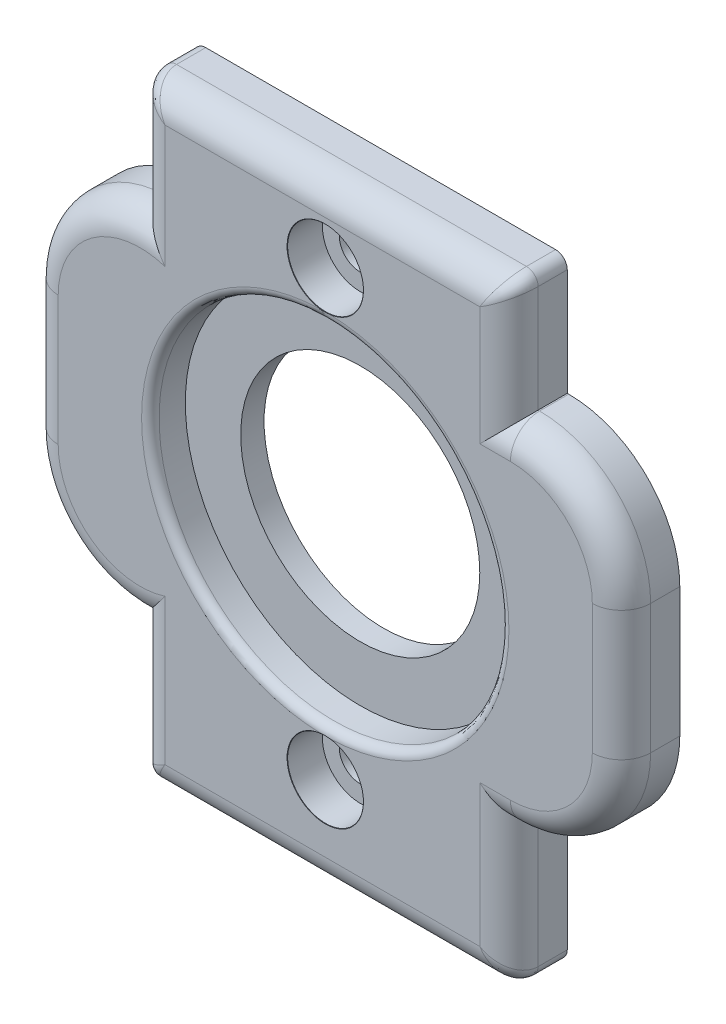
SolidWorks part; units mm, degrees
ref_plane "Front Plane" through (0, 0, 0) normal (0, 0, 1) x (1, 0, 0)
ref_plane "Top Plane" through (0, 0, 0) normal (0, 1, 0) x (1, 0, 0)
ref_plane "Right Plane" through (0, 0, 0) normal (1, 0, 0) x (0, 0, -1)
sketch "Sketch1" plane through (0, 0, 0) normal (0, 0, 1) x (1, 0, 0)
  line L0 (-13.25, 13.25) -> (14.75, 13.25) construction
  line L5 (14.75, -39.25) -> (-15.25, -39.25) construction
  line L6 (15.75, 12.25) -> (15.75, -38.25) construction
  line L7 (-15.25, 13.25) -> (14.75, 13.25)
  line L8 (14.75, -39.25) -> (-15.25, -39.25)
  line L9 (15.75, 12.25) -> (15.75, -38.25)
  line L10 (-16.25, 12.25) -> (-16.25, -38.25)
  arc A0 (15.75, 12.25) -> (14.75, 13.25) centre (14.75, 12.25) ccw construction
  arc A1 (-16.25, 12.25) -> (-15.25, 13.25) centre (-15.25, 12.25) cw
  arc A2 (-16.25, -38.25) -> (-15.25, -39.25) centre (-15.25, -38.25) ccw construction
  arc A3 (14.75, -39.25) -> (15.75, -38.25) centre (14.75, -38.25) ccw construction
  arc A4 (15.75, 12.25) -> (14.75, 13.25) centre (14.75, 12.25) ccw
  arc A6 (-16.25, -38.25) -> (-15.25, -39.25) centre (-15.25, -38.25) ccw
  arc A7 (14.75, -39.25) -> (15.75, -38.25) centre (14.75, -38.25) ccw
  dimension "D1" = 1
extrude "Boss-Extrude1" add sketch "Sketch1" along normal blind 5
sketch "Sketch6" plane through (0, 0, 0) normal (0, 0, 1) x (1, 0, 0)
  line L0 (15.875, 3.0748) -> (14.732, 3.0748) construction
  line L1 (14.732, 3.0748) -> (14.732, -27.075) construction
  line L2 (14.732, -27.075) -> (15.875, -27.075) construction
  line L3 (25.4, -17.55) -> (25.4, -6.4502) construction
  line L4 (-14.732, -27.075) -> (-14.732, 3.0748) construction
  line L5 (-14.732, 3.0748) -> (-15.875, 3.0748) construction
  line L6 (-25.4, -6.4502) -> (-25.4, -17.55) construction
  line L7 (-15.875, -27.075) -> (-14.732, -27.075) construction
  line L8 (15.875, 3.0748) -> (14.732, 3.0748)
  line L9 (14.732, 3.0748) -> (14.732, -27.075)
  line L10 (14.732, -27.075) -> (15.875, -27.075)
  line L11 (25.4, -17.55) -> (25.4, -6.4502)
  line L12 (-14.732, -27.075) -> (-14.732, 3.0748)
  line L13 (-14.732, 3.0748) -> (-15.875, 3.0748)
  line L14 (-25.4, -6.4502) -> (-25.4, -17.55)
  line L15 (-15.875, -27.075) -> (-14.732, -27.075)
  arc A0 (15.875, -27.075) -> (25.4, -17.55) centre (15.875, -17.55) ccw construction
  arc A1 (25.4, -6.4502) -> (15.875, 3.0748) centre (15.875, -6.4502) ccw construction
  arc A2 (-15.875, 3.0748) -> (-25.4, -6.4502) centre (-15.875, -6.4502) ccw construction
  arc A3 (-25.4, -17.55) -> (-15.875, -27.075) centre (-15.875, -17.55) ccw construction
  arc A4 (15.875, -27.075) -> (25.4, -17.55) centre (15.875, -17.55) ccw
  arc A5 (25.4, -6.4502) -> (15.875, 3.0748) centre (15.875, -6.4502) ccw
  arc A6 (-15.875, 3.0748) -> (-25.4, -6.4502) centre (-15.875, -6.4502) ccw
  arc A7 (-25.4, -17.55) -> (-15.875, -27.075) centre (-15.875, -17.55) ccw
sketch "Sketch7" plane through (0, 0, 5) normal (0, 0, 1) x (1, 0, 0)
  line L0 (-14.732, 3.0748) -> (14.732, 3.0748)
  line L1 (-14.732, -27.075) -> (14.732, -27.075)
  line L4 (15.875, 3.0748) -> (14.732, 3.0748)
  line L5 (14.732, 3.0748) -> (14.732, -27.075)
  line L6 (14.732, -27.075) -> (15.875, -27.075)
  line L7 (25.4, -17.55) -> (25.4, -6.4502)
  line L8 (15.875, 3.0748) -> (14.732, 3.0748)
  line L9 (14.732, 3.0748) -> (14.732, -27.075) construction
  line L10 (14.732, -27.075) -> (15.875, -27.075)
  line L11 (25.4, -17.55) -> (25.4, -6.4502)
  line L12 (-14.732, 3.0748) -> (-15.875, 3.0748)
  line L13 (-14.732, -27.075) -> (-14.732, 3.0748)
  line L14 (-15.875, -27.075) -> (-14.732, -27.075)
  line L15 (-25.4, -6.4502) -> (-25.4, -17.55)
  line L16 (-14.732, 3.0748) -> (-15.875, 3.0748)
  line L17 (-14.732, -27.075) -> (-14.732, 3.0748) construction
  line L18 (-15.875, -27.075) -> (-14.732, -27.075)
  line L19 (-25.4, -6.4502) -> (-25.4, -17.55)
  arc A2 (15.875, -27.075) -> (25.4, -17.55) centre (15.875, -17.55) ccw
  arc A3 (25.4, -6.4502) -> (15.875, 3.0748) centre (15.875, -6.4502) ccw
  arc A4 (15.875, -27.075) -> (25.4, -17.55) centre (15.875, -17.55) ccw
  arc A5 (25.4, -6.4502) -> (15.875, 3.0748) centre (15.875, -6.4502) ccw
  arc A6 (-25.4, -17.55) -> (-15.875, -27.075) centre (-15.875, -17.55) ccw
  arc A7 (-15.875, 3.0748) -> (-25.4, -6.4502) centre (-15.875, -6.4502) ccw
  arc A8 (-25.4, -17.55) -> (-15.875, -27.075) centre (-15.875, -17.55) ccw
  arc A9 (-15.875, 3.0748) -> (-25.4, -6.4502) centre (-15.875, -6.4502) ccw
  dimension "D1" = 0
  dimension "D2" = 0
sketch "Sketch8" plane through (0, 0, 0) normal (0, 0, 1) x (1, 0, 0)
  circle A2 centre (0, 7) radius 1.8
  circle A3 centre (0, -31) radius 1.8
extrude "Cut-Extrude2" cut sketch "Sketch8" along normal blind 8
extrude "Boss-Extrude2" add sketch "Sketch7" against normal blind 5
sketch "Sketch12" plane through (0, 0, 0) normal (0, 0, 1) x (1, 0, 0)
  circle A0 centre (0, -12.0001) radius 10.25
  dimension "D1" = 20.5
extrude "Cut-Extrude3" cut sketch "Sketch12" along normal through all
sketch "Sketch13" plane through (0, 0, 5) normal (0, 0, 1) x (1, 0, 0)
  circle A0 centre (0, -12.0001) radius 15
  dimension "D1" = 30
extrude "Cut-Extrude4" cut sketch "Sketch13" against normal blind 3
hole_wizard "CBORE for M3 SHCS2" positions "Sketch14" profile "Sketch15" counterbore size "M3" standard "ANSI Metric" end condition up to next
sketch "Sketch14" plane through (0, 0, 5) normal (0, 0, 1) x (1, 0, 0)
  point P0 (0, -31)
  point P3 (0, 7)
sketch "Sketch15" plane through (0, -31, 5) normal (1, 0, 0) x (0, -1, 0)
  line L0 (0, 0) -> (0, 5)
  line L1 (0, 5) -> (1.7, 5)
  line L3 (1.7, 5) -> (1.7, 3)
  line L4 (3.25, 3) -> (1.7, 3)
  line L5 (3.25, 3) -> (3.25, 0.025)
  line L6 (3.25, 0.025) -> (3.275, 0)
  line L7 (3.275, 0) -> (0, 0)
  line L8 (-3.25, 0.025) -> (-3.275, 0) construction
  line L11 (0, -6.35) -> (0, 107.95) construction
  dimension "Thru Hole Dia." = 3.4
  dimension "Thru Hole Depth" = 5
  dimension "C'Bore Dia." = 6.5
  dimension "C'Bore Depth" = 3
  dimension "Near C'Sink Dia." = 6.55
  dimension "Near C'Sink Angle" = 90
fillet "Fillet1" radius 0.75 1 edges at (15, -12.0001, 5)
fillet "Fillet2" radius 2.5 18 edges at (-22.7415, -24.1513, 5) (-25.4, -12.0001, 5) (-16.25, 7.6587, 5) (-15.9571, 12.9571, 5) (-0.25, 13.25, 5) (15.4571, 12.9571, 5) (15.8125, -27.075, 5) (15.8125, 3.0748, 5) (22.6102, 0.285, 5) (25.4, -12.0001, 5) (-16.25, -32.6588, 5) (-15.9571, -38.9571, 5) (-0.25, -39.25, 5) (15.4571, -38.9571, 5) (-22.7415, 0.1511, 5) (15.75, 7.6624, 5) (22.6102, -24.2852, 5) (15.75, -32.6625, 5)
